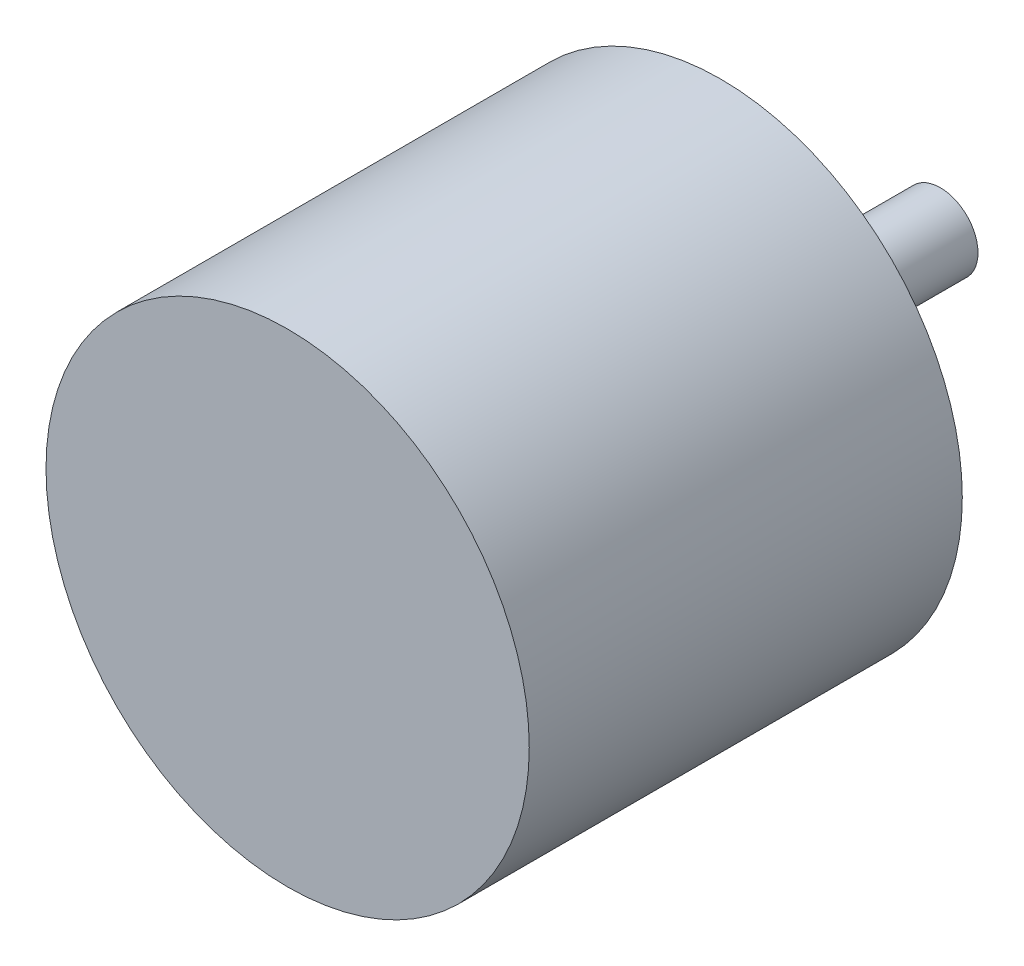
SolidWorks part; units mm, degrees
ref_plane "Front Plane" through (0, 0, 0) normal (0, 0, 1) x (1, 0, 0)
ref_plane "Top Plane" through (0, 0, 0) normal (0, 1, 0) x (1, 0, 0)
ref_plane "Right Plane" through (0, 0, 0) normal (1, 0, 0) x (0, 0, -1)
sketch "Sketch1" plane through (0, 0, 0) normal (0, 0, 1) x (1, 0, 0)
  circle A0 centre (0, 0) radius 19.25
  circle A1 centre (0, 0) radius 10
  circle A2 centre (0, 0) radius 3
  dimension "D1" = 38.5
  dimension "D2" = 20
  dimension "D3" = 6
extrude "Boss-Extrude1" add sketch "Sketch1" along normal blind 34.5 contours A0 A1 | A1 A2 | A2 region at (-18.7055, 0, 0) region at (-9.7172, 0, 0) region at (0, 0, 0)
extrude "Boss-Extrude2" add sketch "Sketch1<3>" against normal blind 5 contours A1 A2 region at (-9.7172, 0, 0)
sketch "Sketch1<3>" plane through (0, 0, 0) normal (0, 0, 1) x (1, 0, 0) same geometry as "Sketch1"
extrude "Boss-Extrude3" add sketch "Sketch1<4>" against normal blind 17.5 contours A2 region at (0, 0, 0)
sketch "Sketch1<4>" plane through (0, 0, 0) normal (0, 0, 1) x (1, 0, 0) same geometry as "Sketch1"
